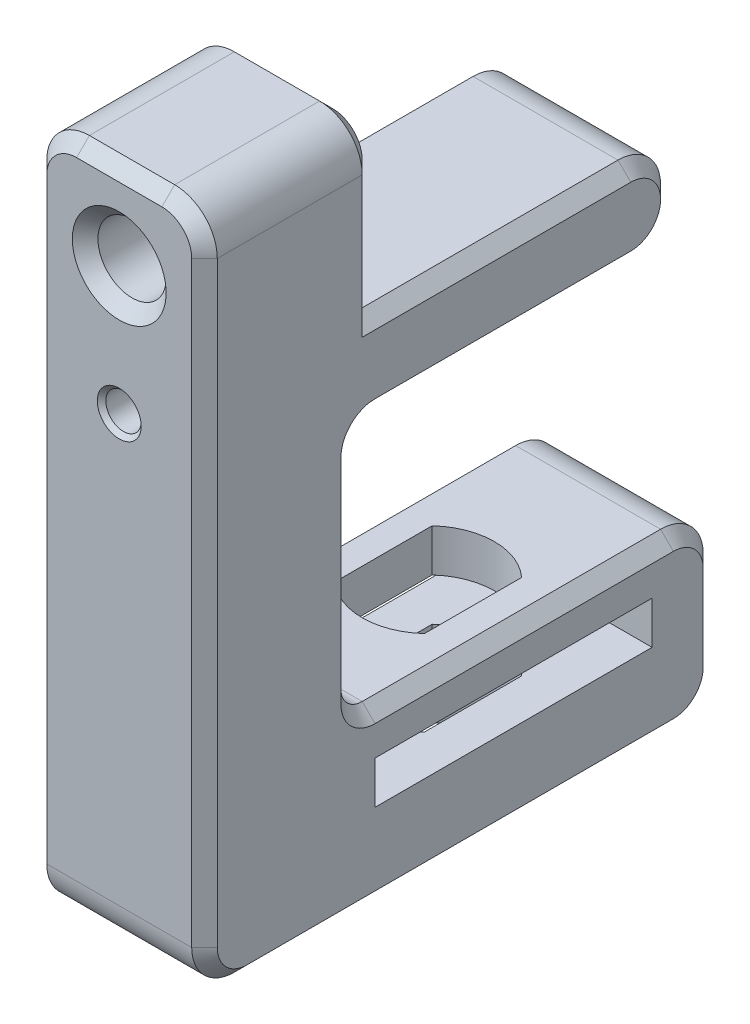
SolidWorks part; units mm, degrees
ref_plane "Front Plane" through (0, 0, 0) normal (0, 0, 1) x (1, 0, 0)
ref_plane "Top Plane" through (0, 0, 0) normal (0, 1, 0) x (1, 0, 0)
ref_plane "Right Plane" through (0, 0, 0) normal (1, 0, 0) x (0, 0, -1)
sketch "Sketch1" plane through (0, 0, 0) normal (1, 0, 0) x (0, 0, -1)
  line L0 (37.5, 30) -> (37.5, 50)
  line L1 (-37.5, -30) -> (37.5, -30) construction
  line L2 (-37.5, -30) -> (-37.5, 30) construction
  line L3 (-37.5, 30) -> (37.5, 30) construction
  line L4 (37.5, -30) -> (37.5, 30) construction
  line L5 (-37.5, -30) -> (37.5, 30) construction
  line L6 (-37.5, 30) -> (37.5, -30) construction
  line L7 (37.5, 50) -> (-57.5, 50)
  line L8 (-57.5, 50) -> (-57.5, -70)
  line L9 (-57.5, -70) -> (37.5, -70)
  line L10 (37.5, -70) -> (37.5, -30)
  line L11 (37.5, -30) -> (-37.5, -30)
  line L12 (-37.5, -30) -> (-37.5, 30)
  line L13 (-37.5, 30) -> (37.5, 30)
  point P0 (0, 0)
  dimension "D1" = 60
  dimension "D2" = 75
  dimension "D3" = 20
  dimension "D4" = 20
  dimension "D5" = 40
extrude "Boss-Extrude1" add sketch "Sketch1" along normal blind 40
sketch "Sketch2" plane through (40, 0, 0) normal (1, 0, 0) x (0, 0, -1)
  line L1 (-32.5, -50) -> (32.5, -50)
  line L2 (-32.5, -50) -> (-32.5, -40)
  line L3 (-32.5, -40) -> (32.5, -40)
  line L4 (32.5, -50) -> (32.5, -40)
  line L5 (-32.5, -50) -> (32.5, -40) construction
  line L6 (-32.5, -40) -> (32.5, -50) construction
  line L7 (37.5, -70) -> (37.5, -30) construction
  line L8 (37.5, -30) -> (-37.5, -30) construction
  line L9 (-57.5, -70) -> (37.5, -70) construction
  point P0 (0, -45)
  dimension "D1" = 5
  dimension "D2" = 10
  dimension "D3" = 10
  dimension "D4" = 20
extrude "Cut-Extrude1" cut sketch "Sketch2" against normal blind 35
sketch "Sketch3" plane through (0, -70, 0) normal (0, -1, 0) x (1, 0, 0)
  line L0 (40, -37.5) -> (0, -37.5) construction
  line L2 (9.5, -11.4018) -> (30.5, -11.4018) construction
  line L3 (9.5, -11.4018) -> (9.5, 11.4018)
  line L4 (9.5, 11.4018) -> (30.5, 11.4018) construction
  line L5 (30.5, -11.4018) -> (30.5, 11.4018)
  line L6 (9.5, -11.4018) -> (30.5, 11.4018) construction
  line L7 (9.5, 11.4018) -> (30.5, -11.4018) construction
  arc A0 (9.5, -11.4018) -> (30.5, -11.4018) centre (20, 0) ccw
  arc A1 (30.5, 11.4018) -> (9.5, 11.4018) centre (20, 0) ccw
  point P5 (20, -37.5)
  dimension "D1" = 31
  dimension "D3" = 21
extrude "Cut-Extrude2" cut sketch "Sketch3" along direction (0, -1, 0) on the side against the normal up to surface (40 mm away) up to face at (20, -30, 0)
sketch "Sketch4" plane through (5, 0, 0) normal (1, 0, 0) x (0, 0, -1)
  line L0 (-32.5, -50) -> (32.5, -50) construction
  line L1 (-27.5, -50) -> (27.5, -50)
  line L2 (-27.5, -50) -> (-27.5, -40)
  line L3 (-27.5, -40) -> (27.5, -40)
  line L4 (27.5, -50) -> (27.5, -40)
  line L5 (-27.5, -50) -> (27.5, -40) construction
  line L6 (-27.5, -40) -> (27.5, -50) construction
  line L7 (32.5, -40) -> (-32.5, -40) construction
  line L8 (32.5, -50) -> (32.5, -40) construction
  point P0 (0, -45)
  point P5 (0, -50)
  point P8 (0, -50)
  dimension "D1" = 5
extrude "Cut-Extrude3" cut sketch "Sketch4" against normal through all
chamfer "Chamfer1" distance 5 angle 45 2 edges at (5, -45, 27.5) (5, -45, -27.5)
sketch "Sketch5" plane through (0, 0, 57.5) normal (0, 0, 1) x (1, 0, 0)
  line L1 (40, 50) -> (0, 50)
  line L2 (40, 50) -> (40, -70)
  line L3 (40, -70) -> (0, -70)
  line L4 (0, 50) -> (0, -70)
extrude "Boss-Extrude2" add sketch "Sketch5" along normal blind 15
sketch "Sketch16" plane through (0, 0, -37.5) normal (0, 0, -1) x (-1, 0, 0)
  line L1 (-40, -30) -> (0, -30)
  line L2 (-40, -30) -> (-40, -70)
  line L3 (-40, -70) -> (0, -70)
  line L4 (0, -30) -> (0, -70)
extrude "Boss-Extrude4" add sketch "Sketch16" along normal blind 10
sketch "Sketch6" plane through (0, -70, 0) normal (0, -1, 0) x (1, 0, 0)
  line L0 (0, 72.5) -> (40, 72.5) construction
  line L1 (40, 72.5) -> (40, -47.5) construction
  circle A0 centre (30, 57.5) radius 4.15
  circle A1 centre (10, 57.5) radius 4.15
  dimension "D1" = 8.3
  dimension "D3" = 10
  dimension "D2" = 15
  dimension "D5" = 20
  dimension "D4" = 2
extrude "Cut-Extrude4" cut sketch "Sketch6" against normal blind 115
chamfer "Chamfer2" distance 1 angle 45 2 edges at (30, -70, 53.35) (10, -70, 53.35)
fillet "Fillet1" radius 10 3 edges at (20, -70, 72.5) (20, -70, -47.5) (20, -30, -47.5)
fillet "Fillet2" radius 5 2 edges at (20, -30, 37.5) (20, 30, 37.5)
sketch "Sketch9" plane through (0, 50, 0) normal (0, 1, 0) x (1, 0, 0)
  line L0 (40, 37.5) -> (40, -72.5) construction
  line L1 (0, -32.5) -> (40, -32.5)
  line L2 (0, -32.5) -> (0, -72.5)
  line L3 (0, -72.5) -> (40, -72.5)
  line L4 (40, -32.5) -> (40, -72.5)
  line L5 (40, -72.5) -> (0, -72.5) construction
  line L6 (0, 37.5) -> (0, -72.5) construction
  point P7 (0, 0)
  point P10 (0, -32.5)
  dimension "D1" = 40
extrude "Boss-Extrude3" add sketch "Sketch9" along normal blind 40
fillet "Fillet3" radius 10 2 edges at (0, 90, 52.5) (40, 90, 52.5)
sketch "Sketch10" plane through (0, 0, 72.5) normal (0, 0, -1) x (-1, 0, 0)
  line L0 (-30, 90) -> (-10, 90) construction
  line L1 (0, 30) -> (0, 50) construction
  circle A0 centre (-20, 70) radius 8
  dimension "D1" = 16
  dimension "D2" = 20
  dimension "D3" = 20
extrude "Cut-Extrude6" cut sketch "Sketch10" along normal blind 20
sketch "Sketch11" plane through (0, 0, 52.5) normal (0, 0, 1) x (1, 0, 0)
  circle A0 centre (20, 70) radius 4.5
  dimension "D1" = 9
extrude "Cut-Extrude7" cut sketch "Sketch11" against normal blind 30
sketch "Sketch12" plane through (0, 0, 72.5) normal (0, 0, 1) x (1, 0, 0)
  line L0 (40, 50) -> (0, 50) construction
  line L1 (40, -60) -> (40, 80) construction
  circle A0 centre (20, 40) radius 4.15
  dimension "D3" = 8.3
  dimension "D1" = 10
  dimension "D2" = 20
extrude "Cut-Extrude8" cut sketch "Sketch12" against normal blind 100
chamfer "Chamfer7" distance 1 angle 45 1 edges at (24.15, 40, 72.5)
fillet "Fillet5" radius 10 1 edges at (20, 30, -37.5)
chamfer "Chamfer10" distance 3 angle 45 1 edges at (12, 70, 72.5)
chamfer "Chamfer11" distance 2 angle 45 1 edges at (20, 65.5, 32.5)
fillet "Fillet6" radius 10 1 edges at (20, 50, -37.5)
chamfer "Chamfer13" distance 3 angle 45 36 edges at (0, 65, 32.5) (2.9289, 87.0711, 32.5) (20, 90, 32.5) (37.0711, 87.0711, 32.5) (40, 65, 32.5) (0, 50, 2.5) (0, 47.0711, -34.5711) (0, 32.9289, -34.5711) (0, 30, 2.5) (0, 28.5355, 36.0355) (0, 0, 37.5) (0, -28.5355, 36.0355) (0, -30, -2.5) (0, -32.9289, -44.5711) (0, -50, -47.5) (0, -67.0711, -44.5711) (0, -70, 12.5) (0, -67.0711, 69.5711) (0, 10, 72.5) (2.9289, 87.0711, 72.5) (20, 90, 72.5) (37.0711, 87.0711, 72.5) (40, 10, 72.5) (40, -67.0711, 69.5711) (40, -70, 12.5) (40, -67.0711, -44.5711) (40, -50, -47.5) (40, -32.9289, -44.5711) (40, -30, -2.5) (40, -28.5355, 36.0355) (40, 50, 2.5) (40, 0, 37.5) (40, 47.0711, -34.5711) (40, 28.5355, 36.0355) (40, 32.9289, -34.5711) (40, 30, 2.5)
sketch "Sketch17" plane through (0, 0, 32.5) normal (0, 0, -1) x (-1, 0, 0)
  circle A0 centre (-20, 70) radius 11
  point P3 (-20, 81)
  point P4 (-10.4737, 64.5)
  point P7 (-29.5263, 64.5)
  point P8 (-20, 70)
  dimension "D1" = 22
  dimension "D2" = 3
hole_wizard "Ø1.5mm Dowel Hole1" positions "Sketch17" profile "Sketch18" hole size "Ø1.5" standard "ISO"
sketch "Sketch18" plane through (29.5263, 64.5, 32.5) normal (1, 0, 0) x (0, 1, 0)
  line L0 (0, 0) -> (0, 20.4506)
  line L1 (0, 20.4506) -> (0.75, 20)
  line L2 (0.75, 20) -> (0.75, 0.025)
  line L3 (0.75, 0.025) -> (0.775, 0)
  line L5 (0.775, 0) -> (0, 0)
  line L6 (-0.75, 0.025) -> (-0.775, 0) construction
  line L10 (0, 20.4506) -> (-0.75, 20) construction
  line L11 (0, -6.35) -> (0, 107.95) construction
  dimension "Hole Dia." = 1.5
  dimension "Hole Depth" = 20
  dimension "Near C'Sink Dia." = 1.55
  dimension "Near C'Sink Angle" = 90
  dimension "Drill Angle" = 118
